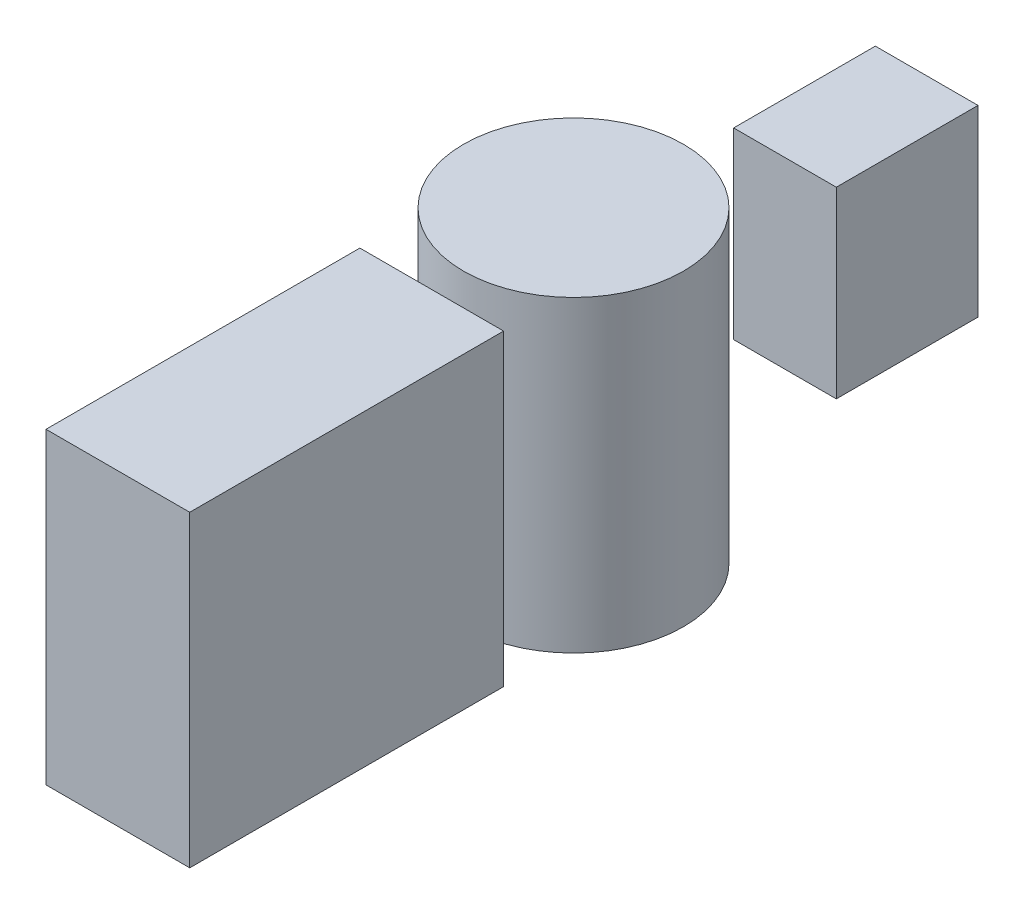
SolidWorks part; units mm, degrees
ref_plane "Front Plane" through (0, 0, 0) normal (0, 0, 1) x (1, 0, 0)
ref_plane "Top Plane" through (0, 0, 0) normal (0, 1, 0) x (1, 0, 0)
ref_plane "Right Plane" through (0, 0, 0) normal (1, 0, 0) x (0, 0, -1)
sketch "Sketch1" plane through (0, 0, 0) normal (1, 0, 0) x (0, 0, -1)
  line L1 (52.3241, 22.6824) -> (87.3787, 22.6824)
  line L2 (52.3241, 22.6824) -> (52.3241, -22.6824)
  line L3 (52.3241, -22.6824) -> (87.3787, -22.6824)
  line L4 (87.3787, 22.6824) -> (87.3787, -22.6824)
  line L5 (52.3241, 22.6824) -> (87.3787, -22.6824) construction
  line L6 (52.3241, -22.6824) -> (87.3787, 22.6824) construction
  point P0 (69.8514, 0)
extrude "Boss-Extrude1" add sketch "Sketch1" along normal mid plane 25.4
sketch "Sketch2" plane through (0, 0, 0) normal (0, 1, 0) x (1, 0, 0)
  line L1 (-17.7812, -35.0778) -> (17.7812, -35.0778)
  line L2 (-17.7812, -35.0778) -> (-17.7812, -112.7356)
  line L3 (-17.7812, -112.7356) -> (17.7812, -112.7356)
  line L4 (17.7812, -35.0778) -> (17.7812, -112.7356)
  line L5 (-17.7812, -35.0778) -> (17.7812, -112.7356) construction
  line L6 (-17.7812, -112.7356) -> (17.7812, -35.0778) construction
  circle A0 centre (0, 0) radius 27.208
  point P3 (0, -73.9067)
  point P8 (14.2976, -89.8701)
  point P9 (0, -95.5786)
  point P10 (-19.0493, -32.7399)
  point P11 (0, -71.0294)
  point P12 (0, -73.9067)
extrude "Boss-Extrude2" add sketch "Sketch2" along normal mid plane 76.2 separate body
sketch "Sketch3" plane through (0, 0, 0) normal (1, 0, 0) x (0, 0, -1)
  line L0 (87.3787, -22.6824) -> (87.3787, 22.6824) construction
  line L1 (92.9237, -4.1109) -> (93.7113, 2.7467)
  line L2 (93.7113, 2.7467) -> (88.1663, 6.8576)
  line L3 (88.1663, 6.8576) -> (81.8337, 4.1109)
  line L4 (81.8337, 4.1109) -> (81.046, -2.7467)
  line L5 (81.046, -2.7467) -> (86.591, -6.8576)
  line L6 (86.591, -6.8576) -> (92.9237, -4.1109)
  line L7 (24.2437, 18.8713) -> (29.5769, 24.2045)
  line L14 (29.5769, 24.2045) -> (40.2433, 11.4869)
  line L15 (40.2433, 11.4869) -> (24.2437, 18.8713)
  circle A0 centre (87.3787, 0) radius 5.9779 construction
ref_axis "Axis3" through (0, 38.1, 0) along (0, -1, 0)
